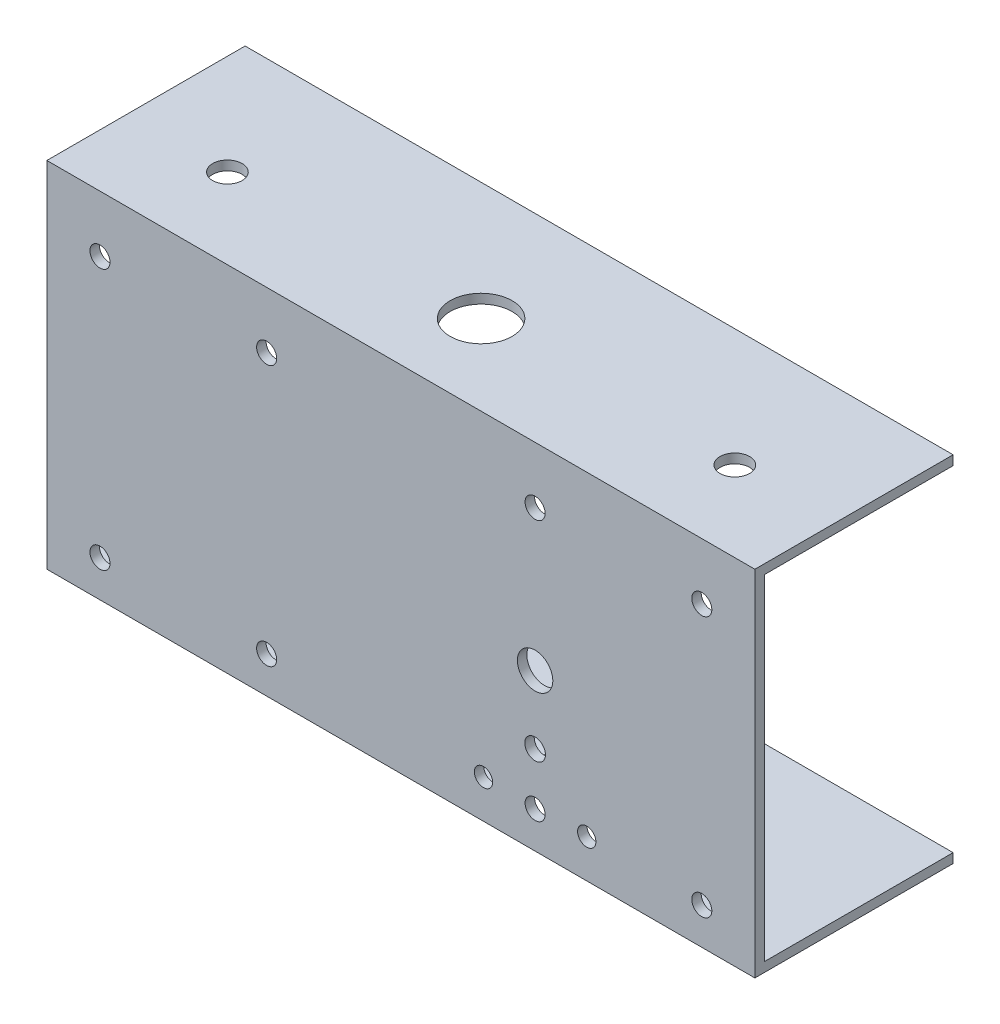
SolidWorks part; units mm, degrees
ref_plane "Front Plane" through (0, 0, 0) normal (0, 0, 1) x (1, 0, 0)
ref_plane "Top Plane" through (0, 0, 0) normal (0, 1, 0) x (1, 0, 0)
ref_plane "Right Plane" through (0, 0, 0) normal (1, 0, 0) x (0, 0, -1)
sketch "Sketch1" plane through (0, 0, 0) normal (0, 1, 0) x (1, 0, 0)
  line L0 (0, -17.6) -> (0, 17.6) construction
  line L13 (34.5, -12) -> (34.5, 13.5)
  line L15 (-60, -12) -> (-60, 20)
  line L16 (-60, 20) -> (60, 20)
  line L17 (60, -12) -> (60, 20)
  line L18 (34.5, 13.5) -> (11, 13.5)
  line L19 (11, 13.5) -> (11, -12)
  line L20 (60, -12) -> (34.5, -12)
  line L21 (11, -12) -> (-60, -12)
  circle A0 centre (0, 0) radius 5.25
  circle A1 centre (-43, 0) radius 2.5
  circle A2 centre (43, 0) radius 2.5
  point P0 (0, 0)
  dimension "D3" = 10.5
  dimension "D4" = 43
  dimension "D5" = 5
  dimension "D1" = 20
  dimension "D2" = 12
  dimension "D6" = 120
  dimension "D7" = 60
  dimension "D9" = 25.5
  dimension "D10" = 23.5
  dimension "D11" = 8.5
other "AlignGroup1"
other "AlignGroup2"
extrude "Boss-Extrude1" add sketch "Sketch1" along normal blind 1.6
sketch "Sketch3" plane through (0, 0, 0) normal (0, -1, 0) x (1, 0, 0)
  line L6 (60, 12) -> (-60, 12)
  line L7 (60, 12) -> (60, 13.6)
  line L8 (60, 13.6) -> (-60, 13.6)
  line L9 (-60, 12) -> (-60, 13.6)
  dimension "D1" = 1.6
extrude "Boss-Extrude3" add sketch "Sketch3" against normal blind 60
ref_plane "Plane1" through (0, 30, 0) normal (0, 1, 0) x (1, 0, 0)
mirror "Mirror1" about plane through (0, 30, 0) normal (0, 1, 0) of "Boss-Extrude1"
sketch "Sketch4" plane through (0, 0, 12) normal (0, 0, 1) x (1, 0, 0)
  line L2 (22.75, 26.5) -> (22.75, 5.2725)
  line L3 (60, 1.6) -> (-60, 1.6) construction
  line L5 (60, 58.4) -> (60, 1.6) construction
  circle A1 centre (22.75, 26.5) radius 3
  circle A5 centre (31.5, 6.5) radius 1.55
  circle A6 centre (14, 6.5) radius 1.55
  circle A7 centre (22.75, 15) radius 1.75
  dimension "D4" = 6
  dimension "D8" = 37.25
  dimension "D13" = 3.5
  dimension "D2" = 3.1
  dimension "D3" = 3.1
  dimension "D5" = 8.75
  dimension "D6" = 8.75
  dimension "D7" = 24.9
  dimension "D12" = 20
  dimension "D14" = 11.5
extrude "Cut-Extrude1" cut sketch "Sketch4" along normal blind 10 contours A1 | A7 L2 | A7 L2 | A5 | A6 region at (23.4927, 15, 12) region at (22.0073, 15, 12) region at (20.6887, 28.5613, 12) region at (31.5, 6.5, 12) region at (14, 6.5, 12)
sketch "Sketch6" plane through (124.2445, 40.7, 12) normal (0, 0, 1) x (1, 0, 0)
  line L0 (-184.2445, -34.5) -> (-64.2445, -34.5)
  line L1 (-101.4945, -14.2) -> (-184.2445, -14.2)
  line L2 (-184.2445, 17.7) -> (-184.2445, -39.1) construction
  line L3 (-129.4945, -59.1) -> (-129.4945, -34.5)
  line L4 (-118.9945, -59.1) -> (-118.9945, -34.5)
  line L5 (-64.2445, 17.7) -> (-64.2445, -39.1) construction
  line L6 (-124.2445, -59.1) -> (-124.2445, -34.5)
  circle A8 centre (-146.9945, -34.5) radius 1.7
  circle A9 centre (-175.2445, -34.5) radius 1.7
  circle A10 centre (-73.2445, -34.5) radius 1.7
  circle A11 centre (-101.4945, -34.5) radius 1.7
  circle A12 centre (-73.2445, 9.7) radius 1.7
  circle A13 centre (-101.4945, 9.7) radius 1.7
  circle A14 centre (-146.9945, 9.7) radius 1.7
  circle A15 centre (-175.2445, 9.7) radius 1.7
  dimension "D3" = 54.75
  dimension "D6" = 44.2
  dimension "D7" = 3.4
  dimension "D8" = 9
  dimension "D9" = 3.4
  dimension "D11" = 3.4
  dimension "D4" = 3.4
  dimension "D5" = 3.4
  dimension "D14" = 3.4
  dimension "D2" = 54.75
  dimension "D10" = 20.3
  dimension "D12" = 17.5
  dimension "D13" = 17.5
extrude "Cut-Extrude2" cut sketch "Sketch6" along normal blind 25 contours A15 | A14 | A13 | A12 | A9 | A8 | A11 | A10 region at (51, 50.4, 12) region at (22.75, 50.4, 12) region at (-22.75, 50.4, 12) region at (-51, 50.4, 12)
sketch "Sketch7" plane through (34.5, 0, 0) normal (-1, 0, 0) x (0, 0, 1)
  line L1 (12, 60) -> (-13.5, 60)
  line L2 (12, 60) -> (12, 58.4)
  line L3 (12, 58.4) -> (-13.5, 58.4)
  line L4 (-13.5, 60) -> (-13.5, 58.4)
extrude "Boss-Extrude4" add sketch "Sketch7" along normal blind 25
